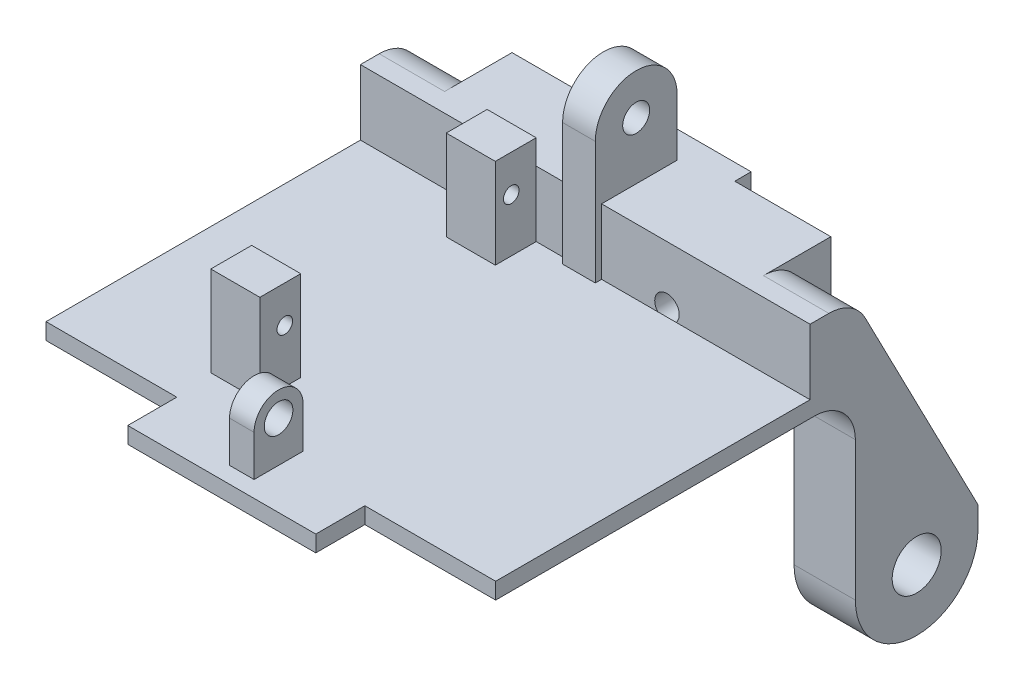
SolidWorks part; units mm, degrees
ref_plane "前视基准面" through (0, 0, 0) normal (0, 0, 1) x (1, 0, 0)
ref_plane "上视基准面" through (0, 0, 0) normal (0, 1, 0) x (1, 0, 0)
ref_plane "右视基准面" through (0, 0, 0) normal (1, 0, 0) x (0, 0, -1)
sketch "草图1" plane through (0, 0, 0) normal (0, 1, 0) x (1, 0, 0)
  line L1 (-27.5, -19.5) -> (27.5, -19.5)
  line L2 (-27.5, -19.5) -> (-27.5, 19.5)
  line L3 (-27.5, 19.5) -> (27.5, 19.5)
  line L4 (27.5, -19.5) -> (27.5, 19.5)
  line L5 (-27.5, -19.5) -> (27.5, 19.5) construction
  line L6 (-27.5, 19.5) -> (27.5, -19.5) construction
  point P0 (0, 0)
  dimension "D1" = 55
  dimension "D2" = 39
extrude "凸台-拉伸1" add sketch "草图1" along normal blind 2
sketch "草图2" plane through (0, 2, 0) normal (0, 1, 0) x (1, 0, 0)
  line L0 (-27.5, -19.5) -> (27.5, -19.5) construction
  line L1 (-11.5, -19.5) -> (11.5, -19.5)
  line L2 (-11.5, -19.5) -> (-11.5, -25.5)
  line L3 (-11.5, -25.5) -> (11.5, -25.5)
  line L4 (11.5, -19.5) -> (11.5, -25.5)
  line L5 (27.5, 19.5) -> (-27.5, 19.5) construction
  point P9 (0, -25.5)
  dimension "D1" = 23
  dimension "D2" = 45
extrude "凸台-拉伸2" add sketch "草图2" against normal blind 2
sketch "草图3" plane through (0, 2, 0) normal (0, 1, 0) x (1, 0, 0)
  line L1 (-6, -14.8415) -> (-12, -14.8415)
  line L2 (-6, -14.8415) -> (-6, -9.8415)
  line L3 (-6, -9.8415) -> (-12, -9.8415)
  line L4 (-12, -14.8415) -> (-12, -9.8415)
  line L6 (-6, 13.9585) -> (-12, 13.9585)
  line L7 (-6, 13.9585) -> (-6, 18.9585)
  line L8 (-6, 18.9585) -> (-12, 18.9585)
  line L9 (-12, 13.9585) -> (-12, 18.9585)
  dimension "D1" = 6
  dimension "D2" = 23.8
  dimension "D3" = 6
  dimension "D4" = 6
  dimension "D5" = 6
  dimension "D6" = 5
  dimension "D7" = 5
extrude "凸台-拉伸3" add sketch "草图3" along normal blind 11
sketch "草图5" plane through (-12, 0, 0) normal (-1, 0, 0) x (0, 0, 1)
  line L0 (-13.9585, 13) -> (-13.9585, 2) construction
  line L1 (9.8415, 13) -> (9.8415, 2) construction
  line L2 (-19.5, 2) -> (19.5, 2) construction
  line L3 (9.8415, 2) -> (14.8415, 2) construction
  circle A0 centre (-15.9085, 8.5) radius 0.95
  circle A1 centre (11.7915, 8.5) radius 0.95
  dimension "D1" = 1.95
  dimension "D2" = 1.95
  dimension "D3" = 6.5
  dimension "D4" = 6.5
  dimension "D5" = 27.7
  dimension "D6" = 1.9
  dimension "D7" = 1.9
extrude "切除-拉伸1" cut sketch "草图5" against normal blind 11
sketch "草图6" plane through (0, 2, 0) normal (0, 1, 0) x (1, 0, 0)
  line L0 (27.5, -19.5) -> (27.5, 19.5) construction
  line L1 (-27.5, 19.5) -> (27.5, 19.5)
  line L2 (-27.5, 19.5) -> (-27.5, 18.9585)
  line L3 (-27.5, 18.9585) -> (27.5, 18.9585)
  line L4 (27.5, 19.5) -> (27.5, 18.9585)
  line L5 (-6, 18.9585) -> (-12, 18.9585) construction
extrude "凸台-拉伸4" add sketch "草图6" along normal blind 8
sketch "草图8" plane through (0, 0, 0) normal (1, 0, 0) x (0, 0, -1)
  line L0 (28.1899, 17) -> (28.1899, 0)
  line L1 (-19.5, 2) -> (18.9585, 2) construction
  line L2 (18.1899, 17) -> (18.1899, 0)
  line L4 (18.1899, 0) -> (28.1899, 0)
  line L7 (-19.5, 0) -> (19.5, 0) construction
  arc A0 (28.1899, 17) -> (18.1899, 17) centre (23.1899, 17) ccw
  circle A1 centre (23.1899, 17) radius 1.65
  dimension "D1" = 15
  dimension "D2" = 10
  dimension "D3" = 3.3
extrude "凸台-拉伸6" add sketch "草图8" along normal mid plane 4
sketch "草图10" plane through (0, 2, 0) normal (0, 1, 0) x (1, 0, 0)
  line L0 (-11.5, -25.5) -> (11.5, -25.5) construction
  line L1 (-1.05, -17.5) -> (1.95, -17.5)
  line L2 (-1.05, -17.5) -> (-1.05, -23.5)
  line L3 (-1.05, -23.5) -> (1.95, -23.5)
  line L4 (1.95, -17.5) -> (1.95, -23.5)
  line L6 (11.5, -25.5) -> (11.5, -19.5) construction
  dimension "D1" = 2
  dimension "D2" = 3
  dimension "D3" = 6
  dimension "D4" = 9.55
extrude "凸台-拉伸7" add sketch "草图10" along normal blind 8
sketch "草图11" plane through (0, 0, -18.9585) normal (0, 0, 1) x (1, 0, 0)
  line L0 (-2, 10) -> (-27.5, 10) construction
  circle A0 centre (-10, 3) radius 1.5
  dimension "D1" = 10
  dimension "D2" = 3
  dimension "D3" = 7
extrude "切除-拉伸3" cut sketch "草图11" against normal blind 13
sketch "草图12" plane through (-27.5, 0, 0) normal (-1, 0, 0) x (0, 0, 1)
  line L1 (-19.5, 0) -> (4.0888, 0)
  line L2 (-19.5, 0) -> (19.5, 0) construction
  line L3 (-19.5, 10) -> (-19.5, 0) construction
  line L4 (-39.5, -22) -> (-39.5, 10)
  line L5 (-19.5, 10) -> (-39.5, 10)
  line L6 (-24.5, -22) -> (-24.5, 0)
  line L7 (-24.5, 0) -> (-19.5, 0)
  line L8 (-19.5, 10) -> (-19.5, 0)
  arc A0 (-39.5, -22) -> (-24.5, -22) centre (-32, -22) ccw
  circle A2 centre (-32, -22) radius 3
  line M7 (-19.5, 10) -> (-19.5, 0)
  dimension "D1" = 15
  dimension "D5" = 6
  dimension "D2" = 22
  dimension "D3" = 12.5
extrude "凸台-拉伸8" add sketch "草图12" against normal blind 7.5 contours L4 A0 L6 L7 L5 A2 M7 region at (-27.5, -7.1737, -31.1527)
sketch "草图13" plane through (0, 0, 0) normal (0, -1, 0) x (1, 0, 0)
  line L0 (-11.5, 25.5) -> (11.5, 25.5) construction
  line L1 (-5, 20) -> (5, 20)
  line L2 (-5, 20) -> (-5, 16.3)
  line L3 (-5, 16.3) -> (5, 16.3)
  line L4 (5, 20) -> (5, 16.3)
  line L5 (-5, 20) -> (5, 16.3) construction
  line L6 (-5, 16.3) -> (5, 20) construction
  point P0 (0, 18.15)
  dimension "D1" = 10
  dimension "D2" = 5.5
  dimension "D3" = 3.7
extrude "凸台-拉伸9" add sketch "草图13" along normal blind 1
mirror "镜向1" about plane through (0, 0, 0) normal (1, 0, 0) of "凸台-拉伸8", "切除-拉伸3"
fillet "圆角3" 2 edges at (0.45, 10, 17.5) (0.45, 10, 23.5) type full round first side face at (0.45, 6, 17.5) second side face at (0.45, 6, 23.5) middle face at (0.45, 10, 20.5)
sketch "草图15" plane through (-1.05, 0, 0) normal (-1, 0, 0) x (0, 0, 1)
  circle A0 centre (20.5, 7) radius 1.75
  dimension "D1" = 3.5
extrude "切除-拉伸5" cut sketch "草图15" against normal blind 23
sketch "草图16" plane through (0, 0, -19.5) normal (0, 0, -1) x (-1, 0, 0)
  line L0 (-20, 10) -> (-2, 10) construction
  line L1 (-7.75, 10) -> (7.75, 10)
  line L2 (-7.75, 10) -> (-7.75, 6)
  line L3 (-7.75, 6) -> (7.75, 6)
  line L4 (7.75, 10) -> (7.75, 6)
  point P6 (0, 6)
  dimension "D1" = 15.5
  dimension "D2" = 4
extrude "凸台-拉伸10" add sketch "草图16" along normal blind 20
sketch "草图17" plane through (0, 0, -19.5) normal (0, 0, -1) x (-1, 0, 0)
  line L6 (-20, 0) -> (-2, 0)
  line L7 (-20, 0) -> (-2, 0)
  line L8 (-20, 10) -> (-20, 0)
  line L10 (-7.75, 6) -> (-7.75, 10)
  line L11 (-7.75, 10) -> (-20, 10)
  line L12 (-2, 0) -> (-2, 6)
  line L14 (-2, 0) -> (-2, 6)
  line L15 (-7.75, 6) -> (-7.75, 10)
  line L16 (-2, 6) -> (-7.75, 6)
  line L18 (-2, 6) -> (-7.75, 6)
  line L21 (-7.75, 10) -> (-20, 10)
  line L32 (-20, 10) -> (-20, 0)
  line L33 (7.75, 6) -> (2, 6)
  line L34 (2, 6) -> (2, 0)
  line L35 (2, 0) -> (20, 0)
  line L36 (20, 0) -> (20, 10)
  line L37 (20, 10) -> (7.75, 10)
  line L38 (7.75, 10) -> (7.75, 6)
  line L39 (7.75, 6) -> (2, 6)
  line L40 (2, 6) -> (2, 0)
  line L41 (2, 0) -> (20, 0)
  line L42 (20, 0) -> (20, 10)
  line L43 (20, 10) -> (7.75, 10)
  line L44 (7.75, 10) -> (7.75, 6)
  circle A0 centre (10, 3) radius 1.5 construction
  circle A1 centre (-10, 3) radius 1.5 construction
  circle A2 centre (10, 3) radius 1.5
  circle A3 centre (-10, 3) radius 1.5
  dimension "D1" = 0
  dimension "D2" = 0
extrude "凸台-拉伸11" add sketch "草图17" along normal blind 10
fillet "圆角4" radius 10 2 edges at (23.75, 10, -39.5) (-23.75, 10, -39.5)
sketch "草图18" plane through (0, 10, 0) normal (0, 1, 0) x (1, 0, 0)
  line L0 (-7.75, 39.5) -> (7.75, 39.5) construction
  line L1 (-14.1233, 41.9545) -> (12.4415, 41.9545)
  line L2 (-14.1233, 41.9545) -> (-14.1233, 31.5)
  line L3 (-14.1233, 31.5) -> (12.4415, 31.5)
  line L4 (12.4415, 41.9545) -> (12.4415, 31.5)
  dimension "D1" = 8
extrude "切除-拉伸6" cut sketch "草图18" against normal blind 10
sketch "草图19" plane through (27.5, 0, 0) normal (1, 0, 0) x (0, 0, -1)
  line L0 (24.3, 10) -> (39.5, -19.3956)
  line L1 (39.5, -22) -> (39.5, 0) construction
  line L2 (24.3, 10) -> (39.5, 10)
  line L3 (39.5, 10) -> (39.5, -19.3956)
  dimension "D1" = 15.2
extrude "切除-拉伸7" cut sketch "草图19" against normal blind 8
sketch "草图20" plane through (-27.5, 0, 0) normal (-1, 0, 0) x (0, 0, 1)
  line L0 (-24.3, 10) -> (-39.5, 10)
  line L1 (-39.5, 10) -> (-39.5, -19.3956)
  line L8 (-39.5, -19.3956) -> (-39.5, -22)
  line L9 (-24.3, 10) -> (-39.5, -19.3956)
  line L10 (-18.9585, 10) -> (-24.3, 10)
  line L11 (-18.9585, 2) -> (-18.9585, 10)
  line L12 (19.5, 2) -> (-18.9585, 2)
  line L13 (19.5, 0) -> (19.5, 2)
  line L14 (-24.5, 0) -> (19.5, 0)
  line L15 (-24.5, -22) -> (-24.5, 0)
  line L17 (-24.3, 10) -> (-39.5, -19.3956)
  arc A1 (-39.5, -22) -> (-24.5, -22) centre (-32, -22) ccw
  dimension "D1" = 0
extrude "切除-拉伸8" cut sketch "草图20" against normal blind 8
fillet "圆角6" radius 5 4 edges at (23.75, 0, -24.5) (-23.75, 0, -24.5) (23.5, 10, -24.3) (-23.5, 10, -24.3)
sketch "草图21" plane through (0, -1, 0) normal (0, -1, 0) x (1, 0, 0)
  line L0 (-11.5, 25.5) -> (11.5, 25.5) construction
  line L1 (-27.5, -19.5) -> (-27.5, 19.5) construction
  circle A0 centre (0, 18.05) radius 1.4
  dimension "D1" = 2.8
  dimension "D2" = 7.45
  dimension "D3" = 27.5
extrude "切除-拉伸9" cut sketch "草图21" against normal blind 4
